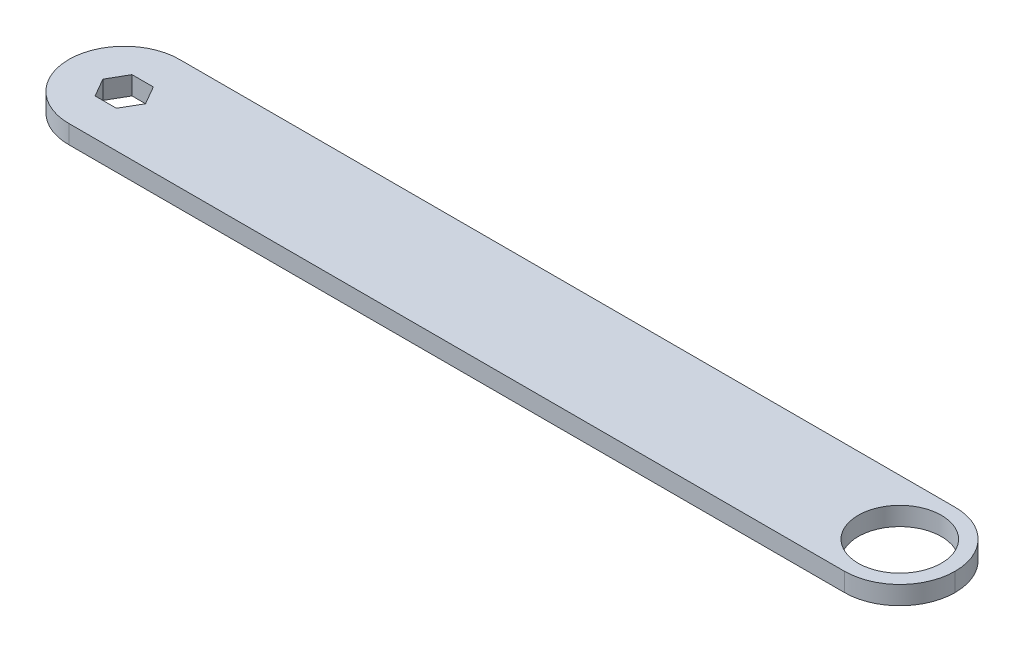
SolidWorks part; units mm, degrees
ref_plane "Front Plane" through (0, 0, 0) normal (0, 0, 1) x (1, 0, 0)
ref_plane "Top Plane" through (0, 0, 0) normal (0, 1, 0) x (1, 0, 0)
ref_plane "Right Plane" through (0, 0, 0) normal (1, 0, 0) x (0, 0, -1)
sketch "Sketch1" plane through (0, 0, 0) normal (0, 1, 0) x (1, 0, 0)
  line L1 (-152.4, -19.05) -> (152.4, -19.05)
  line L2 (-152.4, -19.05) -> (-152.4, 19.05)
  line L3 (-152.4, 19.05) -> (152.4, 19.05)
  line L4 (152.4, -19.05) -> (152.4, 19.05)
  line L5 (-152.4, -19.05) -> (152.4, 19.05) construction
  line L6 (-152.4, 19.05) -> (152.4, -19.05) construction
  point P0 (0, 0)
  dimension "D1" = 38.1
  dimension "D2" = 304.8
extrude "Boss-Extrude1" add sketch "Sketch1" along normal blind 6.35
sketch "Sketch2" plane through (0, 6.35, 0) normal (0, 1, 0) x (1, 0, 0)
  line L0 (152.4, -19.05) -> (152.4, 19.05) construction
  circle A0 centre (133.35, 0) radius 14.3002
  dimension "D1" = 28.6004
  dimension "D2" = 19.05
extrude "Cut-Extrude1" cut sketch "Sketch2" against normal blind 6.35
sketch "Sketch8" plane through (0, 6.35, 0) normal (0, 1, 0) x (1, 0, 0)
  line L0 (152.4, 19.05) -> (-152.4, 19.05) construction
  line L1 (-129.6838, 6.35) -> (-137.0162, 6.35)
  line L2 (-137.0162, 6.35) -> (-140.6823, 0)
  line L3 (-140.6823, 0) -> (-137.0162, -6.35)
  line L4 (-137.0162, -6.35) -> (-129.6838, -6.35)
  line L5 (-129.6838, -6.35) -> (-126.0177, 0)
  line L6 (-126.0177, 0) -> (-129.6838, 6.35)
  line L7 (-152.4, 19.05) -> (-152.4, -19.05) construction
  line L8 (-152.4, -19.05) -> (152.4, -19.05) construction
  circle A0 centre (-133.35, 0) radius 6.35 construction
  dimension "D1" = 12.7
  dimension "D2" = 19.05
  dimension "D3" = 19.05
  dimension "D4" = 0
extrude "Cut-Extrude5" cut sketch "Sketch8" against normal blind 6.35
fillet "Fillet3" radius 19.05 4 edges at (152.4, 3.175, 19.05) (152.4, 3.175, -19.05) (-152.4, 3.175, 19.05) (-152.4, 3.175, -19.05)
